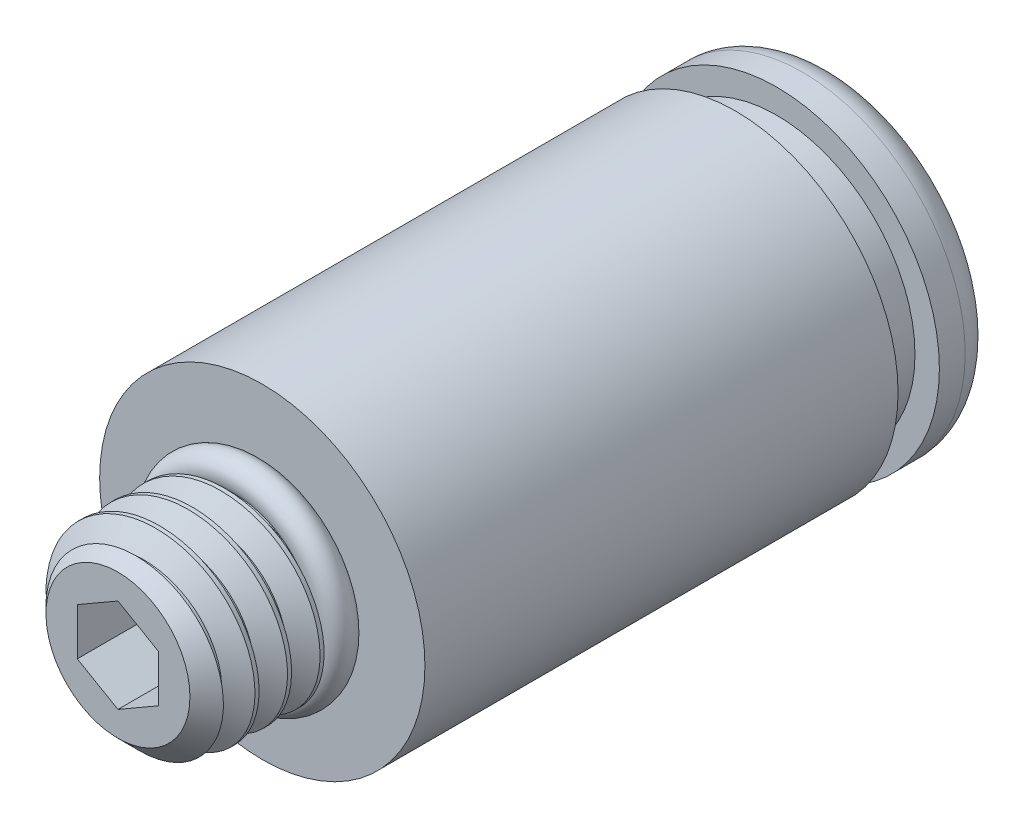
SolidWorks part; units mm, degrees
ref_plane "Front Plane" through (0, 0, 0) normal (0, 0, 1) x (1, 0, 0)
ref_plane "Top Plane" through (0, 0, 0) normal (0, 1, 0) x (1, 0, 0)
ref_plane "Right Plane" through (0, 0, 0) normal (1, 0, 0) x (0, 0, -1)
sketch "Sketch1" plane through (0, 0, 0) normal (0, 0, 1) x (1, 0, 0)
  line L0 (0, 2.3661) -> (0, 2.5) construction
  circle A0 centre (0, 0) radius 2.5 construction
  circle A1 centre (0, 0) radius 2.3661
  dimension "pipe od" = 5
  dimension "D1" = 4.7322
extrude "Extrude1" add sketch "Sketch1" against normal blind 4.3
sketch "Sketch2" plane through (0, 0, 0) normal (0, 0, 1) x (1, 0, 0)
  circle A1 centre (0, 0) radius 2.3661
  circle A2 centre (0, 0) radius 2.3661 construction
  point P4 (0, 2.3661)
curve "Helix/Spiral1" pitch 0.8 height 13.2537 turns 16.5672 parameters "pitch"=0.8
sketch "SketchX" plane through (0, 0, 0) normal (1, 0, 0) x (0, 0, -1)
  line L0 (0, 2.5) -> (4.3, 2.5) construction
  line L1 (4.3, 2.5) -> (0, 2.3661) construction
  line L2 (4.3, 0) -> (17.6, 0) construction
  line L4 (4.3, -2.3661) -> (4.3, 2.3661) construction
  line L5 (0, 2.5) -> (0, 2.3661) construction
  line L6 (0, 0) -> (4.3, 0) construction
  line L7 (4.3, 0) -> (4.3, 2.5) construction
  dimension "D1" = 4.7322
  dimension "D2" = 1.783
  dimension "L1" = 17.6
sketch "Sketch3" plane through (0, 0, 0) normal (1, 0, 0) x (0, 0, -1)
  line L0 (-0.7, 2.3661) -> (-0.4, 1.8465) construction
  line L1 (-0.4, 1.8465) -> (-0.3, 1.8465)
  line L2 (-0.35, 2.3661) -> (-0.35, 2.4527) construction
  line L3 (-0.7, 2.3661) -> (0, 2.3661) construction
  line L4 (-0.35, 2.3661) -> (-0.35, 1.8465) construction
  line L5 (-0.55, 2.1063) -> (-0.15, 2.1063) construction
  line L6 (-0.35, 2.4094) -> (-0.725, 2.4094) construction
  line L7 (-0.725, 2.4094) -> (0.05, 2.4527)
  line L9 (0.05, 2.4527) -> (-0.35, 1.7599) construction
  line L10 (-0.35, 1.7599) -> (-0.75, 2.4527) construction
  line L11 (-0.75, 2.4527) -> (0.05, 2.4527) construction
  line L12 (0.05, 2.4527) -> (-0.3, 1.8465)
  line L13 (-0.4, 1.8465) -> (-0.725, 2.4094)
  line L14 (-0.35, 2.3661) -> (-0.35, 1.7599) construction
  line L15 (-0.35, 2.3661) -> (-1.15, 2.3661) construction
  line L16 (-1.15, 2.3661) -> (-1.95, 2.3661) construction
  line L17 (-1.95, 2.3661) -> (-2.75, 2.3661) construction
  line L19 (4.3, 2.3661) -> (0, 2.3661) construction
  dimension "D2" = 0.1
  dimension "D3" = 0.4
sweep "Cut-Sweep1" cut profiles "Sketch3" path "Helix/Spiral1"
sketch "Sketch4" plane through (0, 0, 0) normal (1, 0, 0) x (0, 0, -1)
  line L0 (0, 0) -> (4.3, 0) construction
  line L1 (4.3, 2.585) -> (0.05, 2.4527) construction
  line L2 (-0.35, 1.7599) -> (4.3, 1.9047) construction
  line L3 (-0.7, 2.3661) -> (0, 2.3661) construction
  line L5 (4.3, 1.8798) -> (3.5, 1.8798)
  line L6 (3.5, 1.8798) -> (2.7947, 2.585)
  line L7 (4.3, 1.8798) -> (4.3, 2.585)
  line L8 (4.3, 2.585) -> (2.7947, 2.585)
  line L9 (0.8142, 2.585) -> (0, 1.7708)
  line L10 (0, 1.7708) -> (0, 2.585)
  line L11 (0.8142, 2.585) -> (0, 2.585)
  line L12 (0, 2.3661) -> (0, -2.3661) construction
  line L13 (4.3, -2.2024) -> (4.3, 0) construction
  line L14 (0, 2.3661) -> (0, 1.6883) construction
  dimension "D1" = 1.783
  dimension "D2" = 45
  dimension "D3" = 0.8
  dimension "D4" = 45
revolve "Cut-Revolve1" cut sketch "Sketch4" angle 360 about L0
sketch "Sketch8" plane through (0, 0, 0) normal (1, 0, 0) x (0, 0, -1)
  line L0 (16.203, 4) -> (16.838, 4)
  line L1 (4.3, 4) -> (15.187, 4)
  line L2 (4.3, 4) -> (4.3, 2)
  line L3 (4.3, 2) -> (17.219, 2) construction
  line L4 (17.6, 3.238) -> (17.6, 2.381)
  line L5 (17.219, 2) -> (17.219, 0)
  line L6 (15.187, 4) -> (15.187, 3.4)
  line L7 (15.187, 3.4) -> (16.203, 3.4)
  line L8 (16.203, 4) -> (16.203, 3.4)
  line L9 (17.219, 0) -> (4.3, 0)
  line L10 (0, 0) -> (17.6, 0) construction
  line L11 (4.3, 2) -> (4.3, 0)
  line L12 (17.219, 2) -> (17.6, 2.381)
  arc A0 (16.838, 4) -> (17.6, 3.238) centre (16.838, 3.238) cw
  point P1 (17.6, 2)
  point P20 (17.6, 4)
  dimension "D4" = 0.762
  dimension "D1" = 1.397
  dimension "D2" = 1.016
  dimension "D3" = 6.8
  dimension "D" = 8
  dimension "Tube Size" = 4
revolve "Revolve1" add sketch "Sketch8" angle 360 about L10
sketch "Sketch12" plane through (0, 0, -4.3) normal (0, 0, 1) x (1, 0, 0)
  circle A1 centre (0, 0) radius 4
  circle A2 centre (0, 0) radius 4
  dimension "D1" = 0
extrude "Boss-Extrude1" add sketch "Sketch12" along normal blind 0.75
sketch "Sketch13" plane through (0, 0, 0) normal (1, 0, 0) x (0, 0, -1)
  line L0 (0, 0) -> (17.6, 0) construction
  line L1 (17.6, -3.238) -> (17.6, 3.238) construction
  line L2 (3.55, 4) -> (3.55, -4) construction
  line L3 (-0.3, 1.8465) -> (5.5305, 1.8465) construction
  circle A0 centre (3.175, 2.2215) radius 0.375
  dimension "D1" = 0.75
revolve "Revolve3" add sketch "Sketch13" angle 360 about L0
sketch "Sketch11" plane through (0, 0, -17.6) normal (0, 0, -1) x (-1, 0, 0)
  circle A1 centre (0, 0) radius 2
extrude "Cut-Extrude4" cut sketch "Sketch11" against normal blind 13.3
sketch "Sketch9" plane through (0, 0, -4.3) normal (0, 0, -1) x (-1, 0, 0)
  line L1 (0, 1.1547) -> (-1, 0.5774)
  line L2 (-1, 0.5774) -> (-1, -0.5774)
  line L3 (-1, -0.5774) -> (0, -1.1547)
  line L4 (0, -1.1547) -> (1, -0.5774)
  line L5 (1, -0.5774) -> (1, 0.5774)
  line L6 (1, 0.5774) -> (0, 1.1547)
  circle A0 centre (0, 0) radius 1 construction
  dimension "H" = 2
extrude "Cut-Extrude1" cut sketch "Sketch9" against normal through all
sketch "Sketch10" plane through (0, 0, 0) normal (1, 0, 0) x (0, 0, -1)
  line L0 (17.219, 2) -> (4.3, 2)
  line L1 (4.3, 2) -> (4.3, 1.1547)
  line L2 (4.3, 1.1547) -> (0, 1.1547)
  line L3 (0, -1.1547) -> (4.3, -1.1547)
  line L4 (4.3, -1.1547) -> (4.3, -2)
  line L5 (4.3, -2) -> (17.219, -2)
  line L6 (17.219, 2) -> (17.6, 2.381)
  line L7 (17.219, -2) -> (17.6, -2.381)
  line L8 (4.3, -2) -> (4.3, 2) construction
  line L11 (17.6, 3.238) -> (17.6, 2.381) construction
  line L12 (4.3, 2) -> (17.219, 2) construction
equation "\"D1@Sketch1\" = \"D1@SketchX\""
equation "\"D2@Sketch3\" = \"pitch@Helix/Spiral1\"*.125"
equation "\"D3@Sketch3\" = \"pitch@Helix/Spiral1\"*.5"
equation "\"D3@Sketch4\" = \"pitch@Helix/Spiral1\"*1"
equation "\"TL@Extrude1\" = \"L1@SketchX\"-\"M@Cut-Extrude4\""
equation "\"D3@Sketch8\" = \"D@Sketch8\"*.85"
